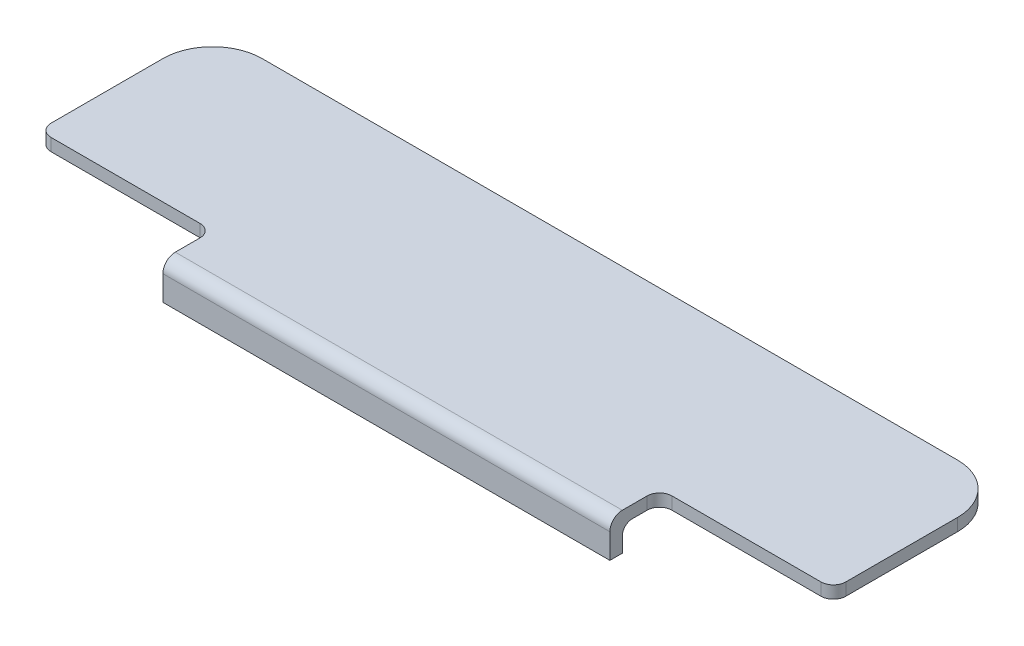
SolidWorks part; units mm, degrees
ref_plane "前视基准面" through (0, 0, 0) normal (0, 0, 1) x (1, 0, 0)
ref_plane "上视基准面" through (0, 0, 0) normal (0, 1, 0) x (1, 0, 0)
ref_plane "右视基准面" through (0, 0, 0) normal (1, 0, 0) x (0, 0, -1)
other "Configuration Table"
sketch "草图1" plane through (0, 0, 0) normal (0, 1, 0) x (1, 0, 0)
  line L1 (-160, -45) -> (160, -45)
  line L2 (-160, -45) -> (-160, 45)
  line L3 (-160, 45) -> (160, 45)
  line L4 (160, -45) -> (160, 45)
  line L5 (-160, -45) -> (160, 45) construction
  line L6 (-160, 45) -> (160, -45) construction
  point P0 (0, 0)
  dimension "D1" = 320
  dimension "D2" = 90
extrude "凸台-拉伸1" add sketch "草图1" along normal blind 5
sketch "草图2" plane through (0, 0, 0) normal (0, -1, 0) x (1, 0, 0)
  line L0 (160, 45) -> (160, -45) construction
  line L1 (-160, 45) -> (160, 45)
  line L2 (-160, 45) -> (-160, 40)
  line L3 (-160, 40) -> (160, 40)
  line L4 (160, 45) -> (160, 40)
  dimension "D1" = 5
extrude "凸台-拉伸2" add sketch "草图2" along normal blind 10
fillet "圆角3" radius 5 1 edges at (0, 5, 45)
fillet "圆角4" radius 4 1 edges at (0, 0, 40)
sketch "草图3" plane through (0, 5, 0) normal (0, 1, 0) x (1, 0, 0)
  line L0 (-160, 45) -> (-160, -40) construction
  line L1 (-160, -25) -> (-90, -25)
  line L2 (-160, -25) -> (-160, -45)
  line L3 (-160, -45) -> (-90, -45)
  line L4 (-90, -25) -> (-90, -45)
  line L5 (160, -45) -> (-160, -45) construction
  line L6 (0, 0) -> (0, -45) construction
  line L7 (160, -45) -> (90, -45)
  line L8 (90, -25) -> (90, -45)
  line L9 (160, -25) -> (90, -25)
  line L10 (160, -25) -> (160, -45)
  dimension "D1" = 20
  dimension "D2" = 70
extrude "切除-拉伸1" cut sketch "草图3" against normal blind 33
fillet "圆角5" radius 5 4 edges at (160, 2.5, 25) (90, 2.5, 25) (-160, 2.5, 25) (-90, 2.5, 25)
fillet "圆角6" radius 20 2 edges at (-160, 2.5, -45) (160, 2.5, -45)
